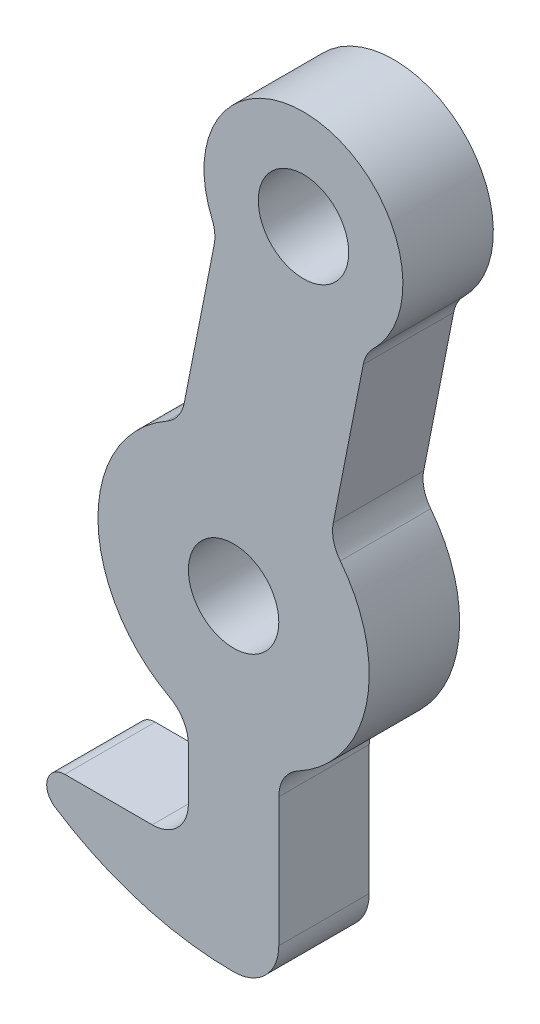
SolidWorks part; units mm, degrees
ref_plane "Front Plane" through (0, 0, 0) normal (0, 0, 1) x (1, 0, 0)
ref_plane "Top Plane" through (0, 0, 0) normal (0, 1, 0) x (1, 0, 0)
ref_plane "Right Plane" through (0, 0, 0) normal (1, 0, 0) x (0, 0, -1)
sketch "Sketch1" plane through (0, 0, 0) normal (0, 0, 1) x (1, 0, 0)
  line L0 (6.7583, 6.712) -> (9.2699, 19.4658)
  line L1 (-3.7087, 8.7733) -> (-1.1971, 21.5271)
  line L3 (3.175, -8.9803) -> (3.175, -19.685)
  line L4 (0, 0) -> (4.9078, 24.9213) construction
  line L7 (0, -19.685) -> (0, 0) construction
  line L9 (-3.175, -8.9803) -> (-3.175, -16.7736)
  line L11 (-12.9813, -16.7736) -> (-15.5314, -16.7736) construction
  line L12 (-3.175, -16.7736) -> (-15.5314, -16.7736)
  arc A0 (3.175, -8.9803) -> (6.7583, 6.712) centre (0, 0) ccw
  circle A1 centre (4.9078, 24.9213) radius 3.175
  arc A2 (0, -22.86) -> (3.175, -19.685) centre (0, -19.685) ccw
  arc A3 (9.2699, 19.4658) -> (-1.1971, 21.5271) centre (4.9078, 24.9213) ccw
  circle A4 centre (0, 0) radius 3.175
  arc A6 (-3.7087, 8.7733) -> (-3.175, -8.9803) centre (0, 0) ccw
  arc A7 (0, -22.86) -> (-15.5314, -16.7736) centre (0, 0) cw
  dimension "D1" = 6.35
  dimension "D3" = 6.35
  dimension "D4" = 19.05
  dimension "D5" = 13.97
  dimension "D7" = 22.86
  dimension "D2" = 6.35
  dimension "D6" = 10.668
  dimension "D8" = 25.4
extrude "Boss-Extrude1" add sketch "Sketch1" along normal mid plane 6.35
fillet "Fillet1" radius 2.54 7 edges at (9.2699, 19.4658, 0) (-1.1971, 21.5271, 0) (-3.7087, 8.7733, 0) (6.7583, 6.712, 0) (3.175, -8.9803, 0) (-3.175, -8.9803, 0) (-3.175, -16.7736, 0)
fillet "Fillet2" radius 1.27 1 edges at (-15.5314, -16.7736, 0)
